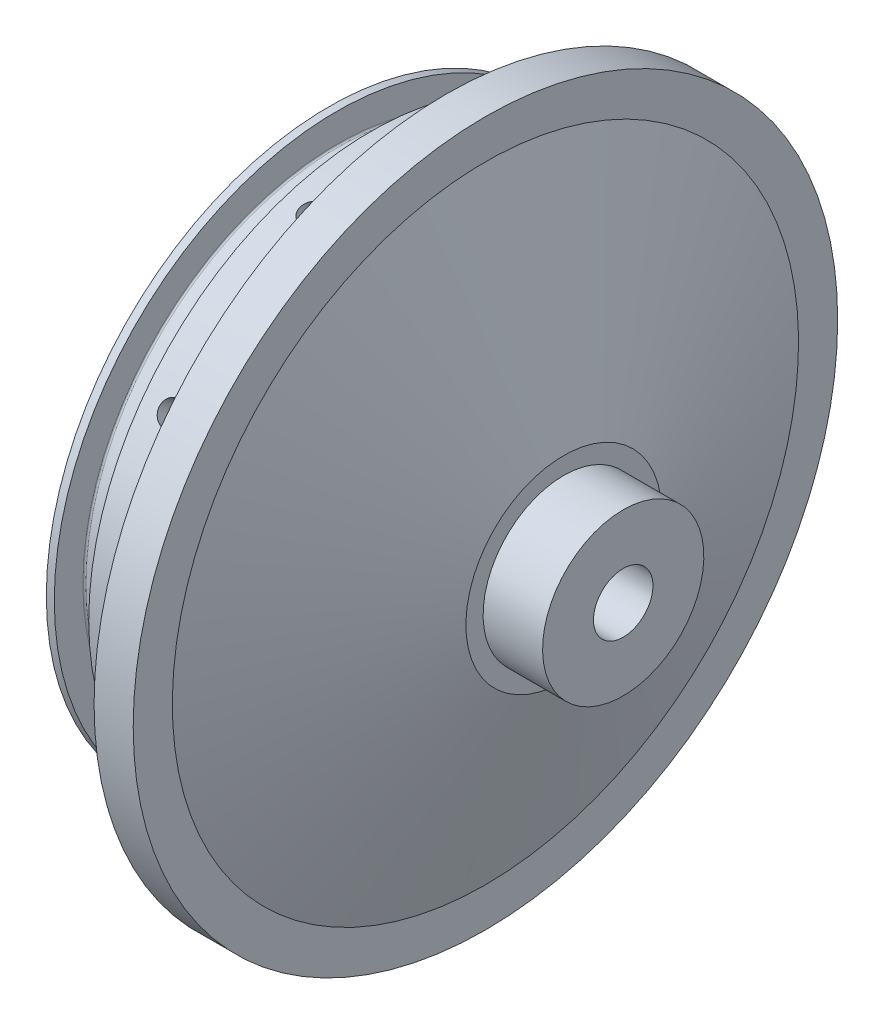
SolidWorks part; units mm, degrees
material "7075-T6 (SN)"
ref_plane "Front Plane" through (0, 0, 0) normal (0, 0, 1) x (1, 0, 0)
ref_plane "Top Plane" through (0, 0, 0) normal (0, 1, 0) x (1, 0, 0)
ref_plane "Right Plane" through (0, 0, 0) normal (1, 0, 0) x (0, 0, -1)
sketch "Sketch1" plane through (0, 0, 0) normal (1, 0, 0) x (0, 0, -1)
  circle A0 centre (0, 0) radius 57.15
  dimension "D1" = 114.3
extrude "Boss-Extrude1" add sketch "Sketch1" along normal blind 6.35
sketch "Sketch2" plane through (0, 0, 0) normal (-1, 0, 0) x (0, 0, 1)
  circle A0 centre (0, 0) radius 45.847
  dimension "D1" = 91.694
extrude "Boss-Extrude2" add sketch "Sketch2" along normal blind 19.05
sketch "Sketch3" plane through (-19.05, 0, 0) normal (-1, 0, 0) x (0, 0, 1)
  circle A0 centre (0, 0) radius 38.227
  dimension "D1" = 76.454
extrude "Cut-Extrude1" cut sketch "Sketch3" against normal blind 6.604
sketch "Sketch5" plane through (0, 0, 0) normal (0, 0, 1) x (1, 0, 0)
  line L0 (6.35, -50.8) -> (19.05, -15.875)
  line L1 (6.35, -57.15) -> (6.35, 57.15) construction
  line L2 (6.35, 0) -> (19.05, 0)
  line L3 (19.05, 0) -> (19.05, -15.875)
  line L4 (6.35, -50.8) -> (6.35, 0)
  dimension "D1" = 50.8
  dimension "D2" = 15.875
  dimension "D3" = 12.7
revolve "Revolve1" add sketch "Sketch5" angle 360 about L2
sketch "Sketch6" plane through (19.05, 0, 0) normal (1, 0, 0) x (0, 0, -1)
  circle A0 centre (0, 0) radius 13.081
  dimension "D1" = 26.162
extrude "Boss-Extrude3" add sketch "Sketch6" along normal blind 9.652
sketch "Sketch7" plane through (28.702, 0, 0) normal (1, 0, 0) x (0, 0, -1)
  circle A0 centre (0, 0) radius 4.826
  dimension "D1" = 9.652
extrude "Cut-Extrude2" cut sketch "Sketch7" against normal through all
sketch "Sketch8" plane through (0, 0, 0) normal (0, 0, 1) x (1, 0, 0)
  line L0 (0, 0) -> (-12.446, 0)
  line L1 (-12.446, 38.227) -> (-12.446, -38.227) construction
  line L2 (-12.446, 0) -> (-12.446, -29.21)
  line L4 (10.414, 0) -> (0, 0)
  line L6 (10.414, -15.875) -> (10.414, 0)
  line L7 (-12.446, -29.21) -> (-2.794, -29.21)
  line L8 (-2.794, -29.21) -> (10.414, -15.875)
  dimension "D1" = 29.21
  dimension "D2" = 12.446
  dimension "D3" = 15.875
  dimension "D4" = 10.414
  dimension "D5" = 9.652
revolve "Cut-Revolve2" cut sketch "Sketch8" angle 360 about L4
fillet "Fillet1" radius 2.032 2 edges at (-2.794, 29.21, 0) (10.414, 15.875, 0)
sketch "Sketch10" plane through (0, 0, 0) normal (0, 1, 0) x (1, 0, 0)
  line L0 (0, 0) -> (-53.2238, 0) construction
  line L1 (-26.2636, 0) -> (26.2636, 0) construction
  line L2 (0, 0) -> (0, 64.5447) construction
  line L3 (0, -62.865) -> (0, 62.865) construction
ref_plane "Plane1" through (0, 0, -45.847) normal (0, 0, -1) x (-1, 0, 0)
sketch "Sketch11" plane through (0, 0, -45.847) normal (0, 0, -1) x (-1, 0, 0)
  line L0 (0, 0) -> (53.2238, 0) construction
  line L1 (0, -45.847) -> (0, 45.847) construction
  circle A0 centre (7.62, 0) radius 1.8986
  dimension "D2" = 3.7973
  dimension "D1" = 7.62
extrude "Cut-Extrude3" cut sketch "Sketch11" against normal blind 10.16
pattern_circular "CirPattern1" count 10 every 36 about axis through (0, 0, 0) along (-1, 0, 0) of "Cut-Extrude3" reverse direction yes
sketch "Sketch13" plane through (0, 0, 0) normal (0, 0, 1) x (1, 0, 0)
  line L0 (-19.05, 0) -> (-19.05, 45.847) construction
  line L1 (-19.05, 38.227) -> (-19.05, -38.227) construction
  line L2 (-19.05, 45.847) -> (0, 45.847) construction
  line L3 (0, 45.847) -> (0, -45.847) construction
  line L4 (0, 0) -> (-64.5609, 0) construction
  line L5 (-17.7575, 45.847) -> (-12.1695, 45.847)
  line L6 (-17.7575, 45.847) -> (-17.7575, 41.2115)
  line L7 (-17.5035, 40.9575) -> (-12.4235, 40.9575)
  line L8 (-12.1695, 45.847) -> (-12.1695, 41.2115)
  arc A0 (-12.4235, 40.9575) -> (-12.1695, 41.2115) centre (-12.4235, 41.2115) ccw
  arc A1 (-17.5035, 40.9575) -> (-17.7575, 41.2115) centre (-17.5035, 41.2115) cw
  point P13 (-12.1695, 40.9575)
  point P16 (-17.7575, 40.9575)
  dimension "D4" = 0.254
  dimension "D1" = 45.847
  dimension "D2" = 5.588
  dimension "D3" = 40.9575
revolve "Cut-Revolve3" cut sketch "Sketch13" angle 360 about L4
sketch "Sketch14" plane through (-12.446, 0, 0) normal (-1, 0, 0) x (0, 0, 1)
  line L0 (0, 0) -> (0, 33.3375) construction
  circle A0 centre (0, 33.3375) radius 1.1303
  dimension "D2" = 2.2606
  dimension "D1" = 33.3375
extrude "Cut-Extrude4" cut sketch "Sketch14" against normal blind 6.35
pattern_circular "CirPattern2" count 8 every 45 about axis through (-12.446, 0, 0) along (1, 0, 0) of "Cut-Extrude4"
